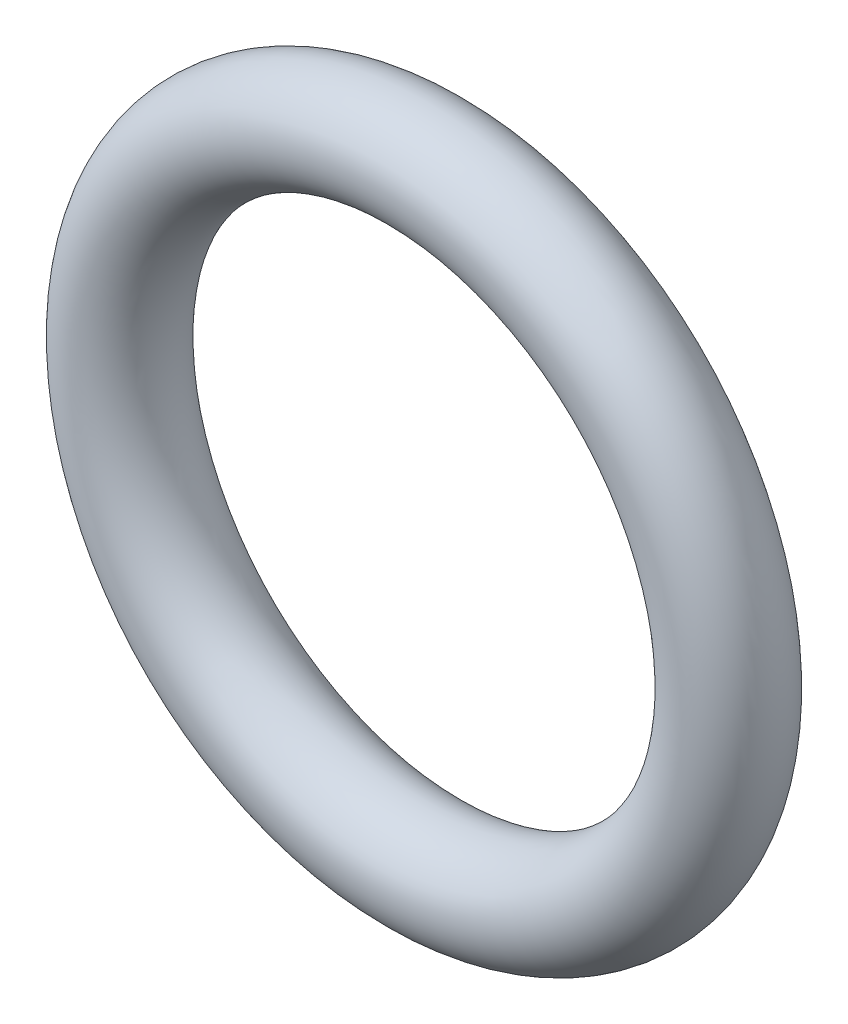
SolidWorks part; units mm, degrees
ref_plane "Front Plane" through (0, 0, 0) normal (0, 0, 1) x (1, 0, 0)
ref_plane "Top Plane" through (0, 0, 0) normal (0, 1, 0) x (1, 0, 0)
ref_plane "Right Plane" through (0, 0, 0) normal (1, 0, 0) x (0, 0, -1)
sketch "Sketch1" plane through (0, 0, 0) normal (1, 0, 0) x (0, 0, -1)
  circle A0 centre (0, 0) radius 2.282
  dimension "D1" = 4.5641
sketch "Sketch2" plane through (0, 0, 0) normal (0, 0, 1) x (1, 0, 0)
  circle A0 centre (0, -13.3945) radius 13.3945
  dimension "D1" = 26.7891
sweep "Sweep1" add profiles "Sketch1" path "Sketch2"
sketch "Sketch3" plane through (0, 0, 0) normal (0, 0, 1) x (1, 0, 0)
  line L0 (-11.1125, -13.3945) -> (11.1125, -13.3945) construction
  line L1 (0, -2.282) -> (0, -24.507) construction
  circle A0 centre (0, -13.3945) radius 11.1125 construction
  point P0 (-4.7625, -23.4348)
  point P1 (4.7625, -23.4348)
  point P5 (-7.7771, -5.457)
  point P6 (7.7771, -5.457)
  dimension "D1" = 9.525
  dimension "D2" = 15.5543
ref_point "Point1"
ref_point "Point2"
ref_point "Point3"
ref_point "Point4"
ref_axis "Axis1" through (7.7771, -5.457, 0) along (-1, 0, 0)
ref_axis "Axis2" through (4.7625, -23.4348, 0) along (-1, 0, 0)
